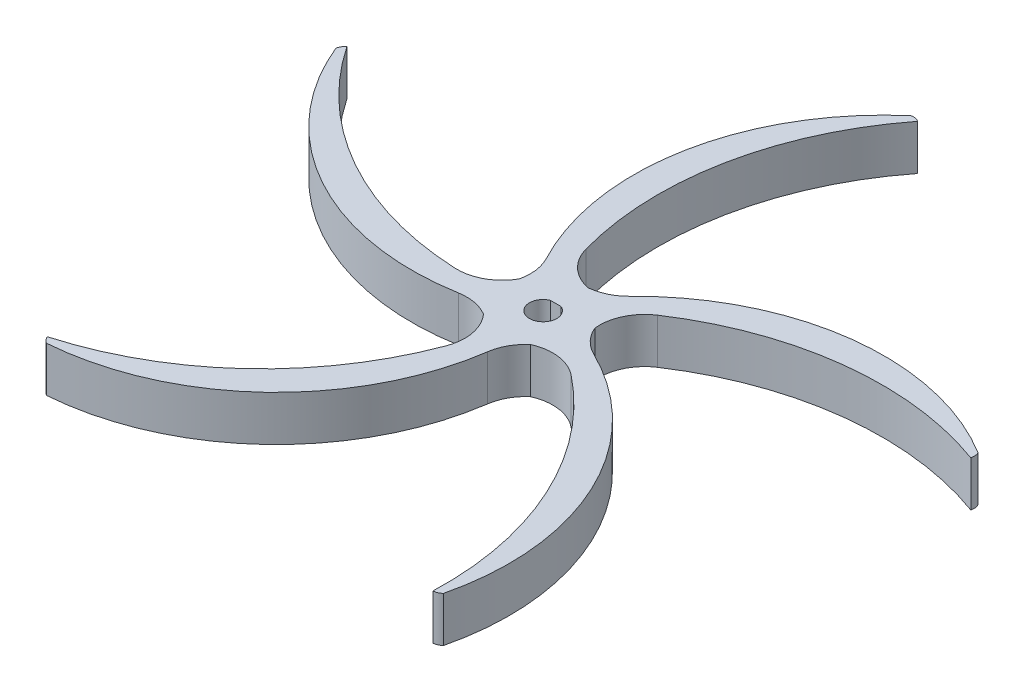
SolidWorks part; units mm, degrees
ref_plane "Front Plane" through (0, 0, 0) normal (0, 0, 1) x (1, 0, 0)
ref_plane "Top Plane" through (0, 0, 0) normal (0, 1, 0) x (1, 0, 0)
ref_plane "Right Plane" through (0, 0, 0) normal (1, 0, 0) x (0, 0, -1)
sketch "Sketch3" plane through (0, 0, 0) normal (0, 1, 0) x (1, 0, 0)
  arc A0 (-2.5686, 0) -> (3.4054, 78.0869) centre (39.1016, 36.084) cw
  arc A1 (-2.5686, 4.6604) -> (5.1443, 77.7019) centre (59.7825, 35.0043) cw
  arc A2 (-2.5686, 0) -> (-2.5686, 4.6604) centre (17.0329, 2.3302) cw
  arc A3 (3.4054, 78.0869) -> (5.1443, 77.7019) centre (3.7694, 75.6113) cw
  point P8 (0, 0)
  point P9 (3.1492, 47.4678)
  point P10 (5.8953, 44.5183)
  point P11 (3.91, 50.0075)
  point P12 (-2.1584, 2.691)
  point P13 (5.4764, 56.7033)
  point P14 (5.4764, 55.7601)
  point P15 (-2.5686, 65.3031)
  point P16 (1.6613, 5.4372)
  point P17 (-2.5686, 0)
  point P18 (-2.5686, 4.6604)
  point P19 (2.8021, 59.1232)
  point P20 (3.9955, 60.516)
  point P21 (0, 73.6544)
  point P22 (1.978, 66.5665)
  point P23 (2.21, 73.6544)
  point P24 (1.3499, 76.2495)
extrude "Boss-Extrude4" add sketch "Sketch3" along normal blind 10
sketch "Sketch5" plane through (0, 0, 0) normal (0, 1, 0) x (1, 0, 0)
  circle A0 centre (0, 0) radius 1.6211
  point P3 (0, 0)
  point P4 (0.3023, -0.5679)
  point P5 (0, 0)
extrude "Boss-Extrude8" add sketch "Sketch5" along normal blind 10 contours A0
pattern_circular "CirPattern4" count 5 over 360 about axis through (0, 10, 0) along (0, 1, 0) of bodies 110 116
sketch "Sketch6" plane through (0, 10, 0) normal (0, 1, 0) x (1, 0, 0)
  circle A0 centre (0, 0) radius 9.3211
extrude "Boss-Extrude9" add sketch "Sketch6" against normal blind 10
sketch "Sketch7" plane through (0, 10, 0) normal (0, 1, 0) x (1, 0, 0)
  line L0 (-1.1926, 2.78) -> (1.1926, 2.78)
  circle A0 centre (0, 0) radius 3.025
  dimension "D1" = 6.05
  dimension "D2" = 2.78
extrude "Cut-Extrude1" cut sketch "Sketch7" against normal blind 10 contours L0 A0 region at (0, 10, 0.0399)
fillet "Fillet1" radius 10 10 edges at (9.2947, 5, 0.7014) (6.6025, 5, -6.5795) (-4.2172, 5, -8.3126) (3.5393, 5, -8.623) (-9.2089, 5, 1.4421) (-7.1073, 5, -6.0308) (-7.9319, 5, 4.8958) (-1.4742, 5, 9.2038) (2.2051, 5, 9.0565) (8.2978, 5, 4.2462)
